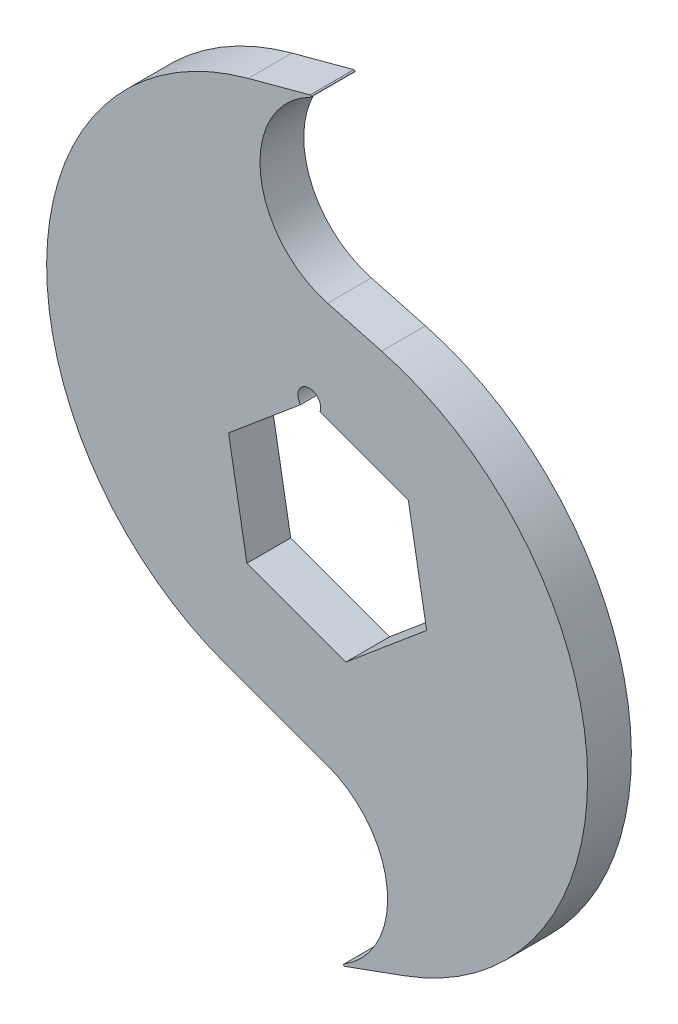
SolidWorks part; units mm, degrees
ref_plane "Front Plane" through (0, 0, 0) normal (0, 0, 1) x (1, 0, 0)
ref_plane "Top Plane" through (0, 0, 0) normal (0, 1, 0) x (1, 0, 0)
ref_plane "Right Plane" through (0, 0, 0) normal (1, 0, 0) x (0, 0, -1)
sketch "Sketch1" plane through (0, 0, 0) normal (0, 0, 1) x (1, 0, 0)
  line L0 (0, 52.07) -> (-11.0405, 49.1117)
  line L1 (0, 52.07) -> (0, 0) construction
  line L2 (0, -52.07) -> (10.7407, -48.1607)
  line L3 (0, 0) -> (0, -52.07) construction
  line L5 (-2.5465, 14.4419) -> (-13.7803, 5.0156)
  line L6 (-13.7803, 5.0156) -> (-11.2338, -9.4263)
  line L7 (-11.2338, -9.4263) -> (2.5465, -14.4419)
  line L8 (2.5465, -14.4419) -> (13.7803, -5.0156)
  line L9 (13.7803, -5.0156) -> (11.2338, 9.4263)
  line L10 (11.2338, 9.4263) -> (-2.5465, 14.4419)
  line L11 (0, 27.5355) -> (7.5237, 25.5195)
  line L12 (0, -28.2018) -> (-14.1906, -23.0368)
  circle A0 centre (0, 0) radius 52.07 construction
  arc A1 (0, 52.07) -> (0, 27.5355) centre (3.287, 39.8027) ccw
  arc A3 (0, -52.07) -> (0, -28.2018) centre (-4.3437, -40.1359) ccw
  arc A4 (10.7407, -48.1607) -> (7.5237, 25.5195) centre (-2.4834, -11.8278) ccw
  arc A5 (-11.0405, 49.1117) -> (-14.1906, -23.0368) centre (-1.2414, 12.5408) ccw
  circle A6 centre (0, 0) radius 12.7 construction
  circle A7 centre (-2.5465, 14.4419) radius 1.5875
  dimension "D4" = 70
  dimension "D5" = 25.4
  dimension "D1" = 104.14
  dimension "D6" = 12.7
  dimension "D8" = 3.175
  dimension "D2" = 11.43
  dimension "D3" = 75
  dimension "D7" = 10
extrude "Boss-Extrude1" add sketch "Sketch1" along normal mid plane 6.096 contours L0 A5 L12 A3 L2 A4 L11 A1 A7 L10 L9 L8 L7 L6 L5 region at (-10.698, 39.8027, 0)
fillet "Fillet1" radius 0.127 2 edges at (0, 52.07, 0) (0, -52.07, 0)
